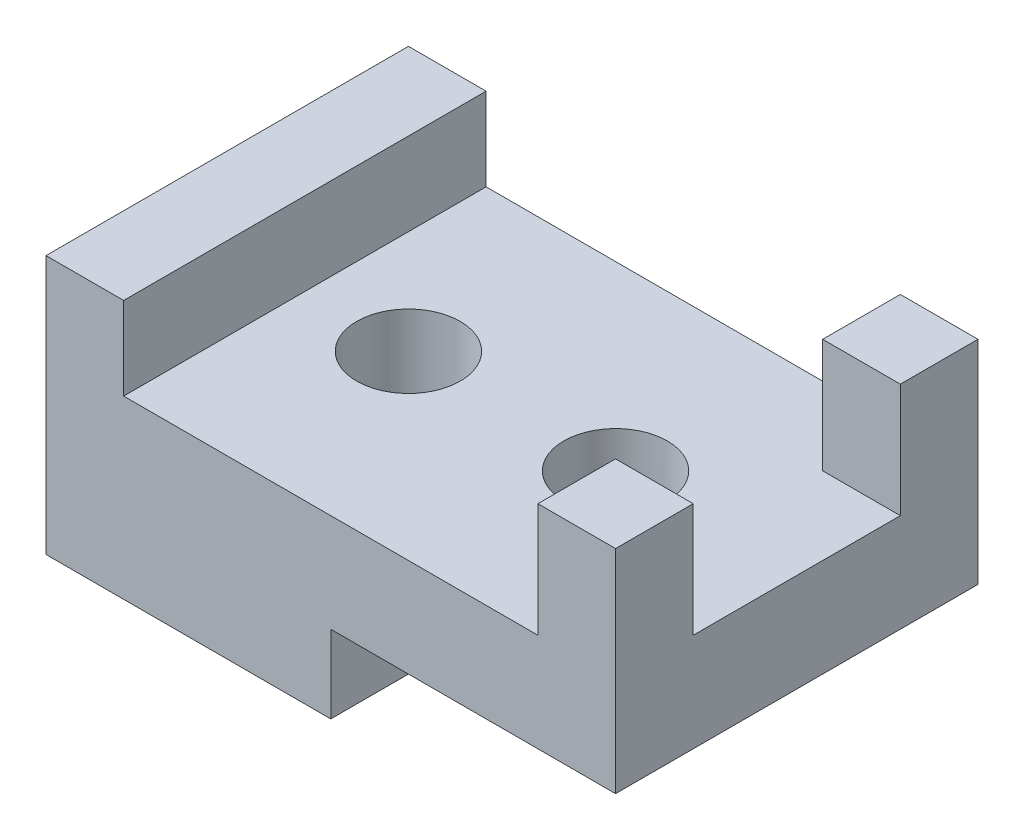
SolidWorks part; units mm, degrees
ref_plane "Plano frontal" through (0, 0, 0) normal (0, 0, 1) x (1, 0, 0)
ref_plane "Plano superior" through (0, 0, 0) normal (0, 1, 0) x (1, 0, 0)
ref_plane "Plano direito" through (0, 0, 0) normal (1, 0, 0) x (0, 0, -1)
sketch "Esboço1" plane through (0, 0, 0) normal (0, 0, 1) x (1, 0, 0)
  line L0 (0, 0) -> (0, -50)
  line L1 (0, -50) -> (55, -50)
  line L2 (110, -35) -> (110, -16)
  line L3 (110, -16) -> (15, -16)
  line L4 (15, -16) -> (15, 0)
  line L5 (15, 0) -> (0, 0)
  line L6 (55, -50) -> (55, -35)
  line L7 (55, -35) -> (110, -35)
  dimension "D1" = 50
  dimension "D2" = 15
  dimension "D3" = 110
  dimension "D4" = 15
  dimension "D5" = 16
  dimension "D6" = 55
extrude "Ressalto-extrusão1" add sketch "Esboço1" along normal blind 70
sketch "Esboço2" plane through (0, -16, 0) normal (0, 1, 0) x (1, 0, 0)
  line L1 (110, -70) -> (95, -70)
  line L2 (110, -70) -> (110, -55)
  line L3 (110, -55) -> (95, -55)
  line L4 (95, -70) -> (95, -55)
  line L5 (110, 0) -> (95, 0)
  line L6 (110, 0) -> (110, -15)
  line L7 (110, -15) -> (95, -15)
  line L8 (95, 0) -> (95, -15)
  dimension "D1" = 15
  dimension "D2" = 15
  dimension "D3" = 15
  dimension "D4" = 15
extrude "Ressalto-extrusão2" add sketch "Esboço2" along normal blind 22
sketch "Esboço3" plane through (0, -16, 0) normal (0, 1, 0) x (1, 0, 0)
  circle A0 centre (35, -35) radius 10
  circle A1 centre (75, -35) radius 10
  point P0 (0, 0)
  dimension "D5" = 20
  dimension "D6" = 20
extrude "Corte-extrusão1" cut sketch "Esboço3" against normal blind 10 contours A0
extrude "Corte-extrusão2" cut sketch "Esboço3<4>" against normal blind 20
sketch "Esboço3<4>" plane through (0, -16, 0) normal (0, 1, 0) x (1, 0, 0) same geometry as "Esboço3"
